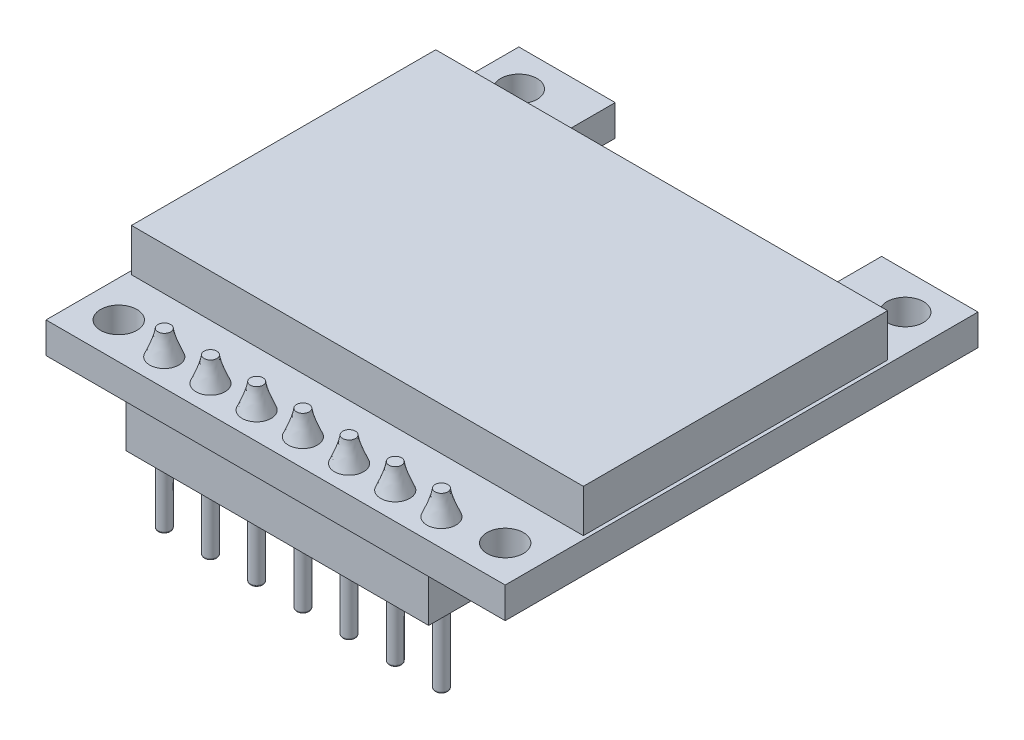
SolidWorks part; units mm, degrees
ref_plane "前视基准面" through (0, 0, 0) normal (0, 0, 1) x (1, 0, 0)
ref_plane "上视基准面" through (0, 0, 0) normal (0, 1, 0) x (1, 0, 0)
ref_plane "右视基准面" through (0, 0, 0) normal (1, 0, 0) x (0, 0, -1)
sketch "草图1" plane through (0, 0, 0) normal (0, 1, 0) x (1, 0, 0)
  line L1 (12.625, -13) -> (-12.625, -13)
  line L2 (12.625, -13) -> (12.625, 13)
  line L3 (12.625, 13) -> (-12.625, 13)
  line L4 (-12.625, -13) -> (-12.625, 13)
  line L5 (12.625, -13) -> (-12.625, 13) construction
  line L6 (12.625, 13) -> (-12.625, -13) construction
  point P0 (0, 0)
extrude "凸台-拉伸1" add sketch "草图1" along normal blind 1.7
sketch "草图3" plane through (0, 0, 0) normal (0, 1, 0) x (1, 0, 0)
  line L0 (-12.625, -13) -> (12.625, -13) construction
  line L1 (12.625, 13) -> (-12.625, 13) construction
  line L3 (-12.625, 13) -> (-12.625, -13) construction
  line L4 (-12.625, 13) -> (-12.625, -13) construction
  line L5 (0, -9.6661) -> (0, 0) construction
  circle A0 centre (-10.625, -11) radius 1
  circle A1 centre (10.625, -11) radius 1
  circle A2 centre (-10.625, 11) radius 1
  circle A3 centre (10.625, 11) radius 1
  dimension "D1" = 2
  dimension "D3" = 2
  dimension "D2" = 2
  dimension "D4" = 2
extrude "切除-拉伸3" cut sketch "草图3" along normal blind 2
sketch "草图7" plane through (0, 1.7, 0) normal (0, 1, 0) x (1, 0, 0)
  line L1 (12.625, -13) -> (12.625, 13) construction
  line L8 (12.425, -8.5) -> (12.425, 8.23)
  line L10 (-12.425, -8.5) -> (-12.425, 8.23)
  line L11 (12.425, -8.5) -> (-12.425, -8.5)
  line L12 (12.425, 8.23) -> (-12.425, 8.23)
  dimension "D3" = 0.2
extrude "凸台-拉伸4" add sketch "草图7" along normal blind 2.35
sketch "草图9" plane through (0, 1.7, 0) normal (0, 1, 0) x (1, 0, 0)
  line L0 (7.325, 13) -> (7.325, 8.23)
  line L1 (12.625, 13) -> (-12.625, 13) construction
  line L2 (12.425, 8.23) -> (-12.425, 8.23) construction
  line L3 (12.625, -13) -> (12.625, 13) construction
  line L4 (0, 0) -> (0, 8.23) construction
  line L5 (12.425, 8.23) -> (-12.425, 8.23) construction
  line L6 (-7.325, 13) -> (-7.325, 8.23)
  line L7 (7.325, 8.23) -> (-7.325, 8.23)
  line L8 (-7.325, 13) -> (7.325, 13)
  dimension "D1" = 5.3
extrude "切除-拉伸5" cut sketch "草图9" against normal blind 1.7
sketch "草图10" plane through (0, 1.7, 0) normal (0, 1, 0) x (1, 0, 0)
  line L0 (0, 0.3698) -> (0, -13) construction
  line L1 (-12.625, -13) -> (12.625, -13) construction
  circle A0 centre (0, -11.5) radius 0.35
  circle A1 centre (2.54, -11.5) radius 0.35
  circle A2 centre (5.08, -11.5) radius 0.35
  circle A3 centre (7.62, -11.5) radius 0.35
  circle A4 centre (-2.54, -11.5) radius 0.35
  circle A5 centre (-5.08, -11.5) radius 0.35
  circle A6 centre (-7.62, -11.5) radius 0.35
  dimension "D1" = 0
  dimension "D2" = 1.5
  dimension "D3" = 2.54
  dimension "D4" = 1.5
  dimension "D5" = 1.5
  dimension "D6" = 1.5
  dimension "D7" = 2.54
  dimension "D8" = 2.54
extrude "凸台-拉伸5" add sketch "草图10" along normal blind 1.36 and the other way blind 8.2
sketch "草图11" plane through (0, 1.7, 0) normal (0, 1, 0) x (1, 0, 0)
  line L0 (0, 0) -> (0, -13) construction
  line L1 (-12.625, -13) -> (12.625, -13) construction
  circle A4 centre (0, -11.5) radius 0.8
  circle A5 centre (7.62, -11.5) radius 0.8
  circle A6 centre (5.08, -11.5) radius 0.8
  circle A7 centre (2.54, -11.5) radius 0.8
  circle A8 centre (-2.54, -11.5) radius 0.8
  circle A9 centre (-5.08, -11.5) radius 0.8
  circle A10 centre (-7.62, -11.5) radius 0.8
  dimension "D1" = 0
  dimension "D2" = 1.5
  dimension "D3" = 2.54
  dimension "D4" = 1.5
  dimension "D5" = 2.54
  dimension "D6" = 2.54
  dimension "D7" = 1.5
  dimension "D8" = 1.5
loft "放样2" add section face at (7.62, 3.06, 11.85) section "草图11" connector at (7.4682, 3.06, 11.1846) connector at (7.9556, 1.7, 10.7738)
pattern_linear "阵列(线性)1" count 7 spacing 2.54 along (-1, 0, 0) of "放样2"
sketch "草图13" plane through (0, 0, 0) normal (0, 1, 0) x (1, 0, 0)
  line L0 (0, 0) -> (0, -13) construction
  line L1 (-12.625, -13) -> (12.625, -13) construction
  line L2 (0.35, -11.5) -> (-0.35, -11.5) construction
  line L4 (-9.18, -10.1) -> (9.18, -10.1)
  line L5 (-9.18, -10.1) -> (-9.18, -12.9)
  line L6 (-9.18, -12.9) -> (9.18, -12.9)
  line L7 (9.18, -10.1) -> (9.18, -12.9)
  line L8 (-9.18, -10.1) -> (9.18, -12.9) construction
  line L9 (-9.18, -12.9) -> (9.18, -10.1) construction
  circle A0 centre (0, -11.5) radius 0.35 construction
  point P9 (0, -11.5)
  point P10 (0, -11.5)
extrude "凸台-拉伸6" add sketch "草图13" against normal blind 2.43
fillet "圆角2" radius 0.5 4 edges at (-9.18, -1.215, 12.9) (-9.18, -1.215, 10.1) (9.18, -1.215, 10.1) (9.18, -1.215, 12.9)
fillet "圆角3" radius 0.1 7 edges at (7.62, -6.5, 11.85) (5.08, -6.5, 11.85) (2.54, -6.5, 11.85) (0, -6.5, 11.85) (-2.54, -6.5, 11.15) (-5.08, -6.5, 11.15) (-7.62, -6.5, 11.15)
sketch "草图14" plane through (0, 0, 0) normal (0, -1, 0) x (1, 0, 0)
  line L0 (-8.32, 10.1) -> (-8.32, 12.9)
  line L1 (-9.18, 10.1) -> (9.18, 10.1) construction
  line L2 (-9.18, 12.9) -> (9.18, 12.9) construction
  line L3 (-8.32, 12.9) -> (-9.18, 12.9)
  line L4 (-9.18, 12.9) -> (-9.18, 10.1)
  line L5 (-9.18, 10.1) -> (-8.32, 10.1)
  line L6 (0, 11.5) -> (0, 12.9) construction
  line L7 (9.18, 10.1) -> (8.32, 10.1)
  line L8 (9.18, 12.9) -> (9.18, 10.1)
  line L9 (8.32, 12.9) -> (9.18, 12.9)
  line L10 (8.32, 10.1) -> (8.32, 12.9)
  circle A0 centre (-7.62, 11.5) radius 0.25 construction
  dimension "D1" = 0.7
extrude "切除-拉伸6" cut sketch "草图14" along normal blind 2.5
